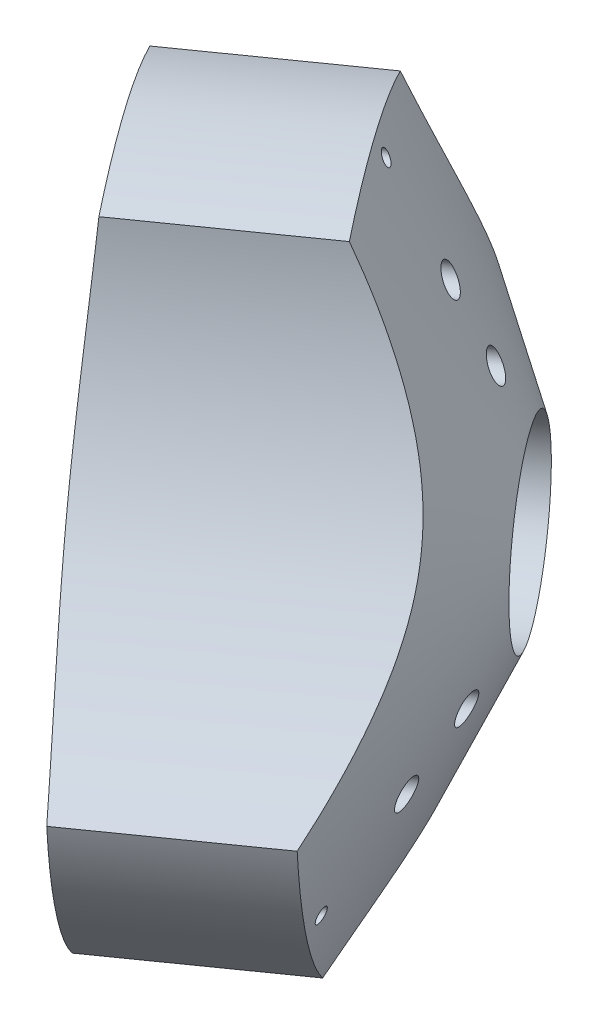
SolidWorks part; units mm, degrees
material "ABS"
ref_plane "前视基准面" through (0, 0, 0) normal (0, 0, 1) x (1, 0, 0)
ref_plane "上视基准面" through (0, 0, 0) normal (0, 1, 0) x (1, 0, 0)
ref_plane "右视基准面" through (0, 0, 0) normal (1, 0, 0) x (0, 0, -1)
other "Configuration Table"
sketch "草图1" plane through (0, 0, 0) normal (0, 1, 0) x (1, 0, 0)
  line L0 (0, 0) -> (50000, 0) construction
  line L1 (0, 0) -> (43301.2702, 25000) construction
  line L2 (0, 0) -> (24999.9997, 43301.2703) construction
  line L3 (0, 0) -> (0, 50000) construction
  line L4 (0, 0) -> (-25000, 43301.2702) construction
  line L5 (0, 0) -> (-43301.2703, 24999.9997) construction
  line L6 (23.1116, -40.0305) -> (43.904, -25.348)
  line L7 (43.904, -25.348) -> (88.4526, -51.0682)
  line L8 (88.4526, -51.0682) -> (46.5626, -80.6488)
  line L9 (46.5626, -80.6488) -> (23.1116, -40.0305)
  line L10 (61.6152, -70.0195) -> (55.8469, -61.8508) construction
  line L11 (55.8469, -61.8508) -> (78.9147, -45.5614)
  line L12 (55.8469, -61.8508) -> (41.5417, -71.9524)
  spline S0 degree 4 poles (4.5441, -13.9852) (5.069, -13.9115) (6.1117, -13.7144) (7.5966, -13.2868) (9.4525, -12.4738) (11.1485, -11.4611) (12.673, -10.2854) (14.0902, -8.9027) (15.2006, -7.528) (16.0517, -6.2294) (16.6357, -5.1571) (16.9969, -4.4036) (17.2795, -3.7437) (17.4701, -3.2541) (17.647, -2.7595) (17.7869, -2.3315) (17.8956, -1.9726) (17.9965, -1.6106) (18.0724, -1.3201) (18.1431, -1.0312) (18.201, -0.7763) (18.2495, -0.5466) (18.2961, -0.3139) (18.338, -0.0934) (18.3688, 0.0809) (18.404, 0.2961) (18.438, 0.517) (18.4698, 0.7375) (18.5019, 0.9839) (18.5336, 1.2626) (18.5616, 1.5443) (18.5855, 1.8273) (18.6051, 2.1103) (18.6204, 2.3933) (18.6344, 2.7473) (18.6427, 3.1726) (18.6402, 3.6687) (18.606, 4.6606) (18.4743, 6.0736) (18.1443, 7.891) (17.4882, 10.0676) (16.5951, 12.1579) (15.4804, 14.1385) (14.1536, 15.9992) (12.6297, 17.7192) (10.7951, 19.3989) (8.6272, 20.9716) (6.1287, 22.3558) (3.3088, 23.4722) (0.3713, 24.2251) (-2.6362, 24.611) (-5.6679, 24.6319) (-8.6804, 24.2953) (-11.6337, 23.6131) (-14.4905, 22.6011) (-17.8988, 20.9477) (-21.6682, 18.3857) (-25.4815, 14.66) (-28.8831, 9.6089) (-31.2279, 3.9916) (-32.5355, -2.3024) (-32.5832, -9.4982) (-30.886, -17.2942) (-27.0418, -25.1548) (-21.1423, -32.1629) (-13.78, -37.6027) (-5.394, -41.2569) (3.5764, -43.0207) (12.7127, -42.8868) (21.6333, -40.9289) (30.0036, -37.2857) (37.5425, -32.1439) (44.0239, -25.7248) (49.277, -18.2707) (53.1837, -10.0336) (55.6748, -1.2666) (56.7255, 7.7843) (56.3496, 16.8863) (54.5948, 25.8236) (51.5367, 34.4007) (47.2736, 42.4454) (41.6252, 50.2165) (33.2939, 58.6988) (21.6024, 66.7973) (6.2316, 72.9489) (-11.9297, 75.3897) (-30.1426, 73.5037) (-47.4501, 67.5662) (-63.0493, 58.0235) (-76.3038, 45.4399) (-86.7456, 30.4509) (-94.067, 13.7235) (-98.1075, -4.0757) (-98.837, -22.3066) (-96.337, -40.374) (-90.7813, -57.7411) (-82.4178, -73.9383) (-71.5503, -88.568) (-58.5225, -101.306) (-43.7037, -111.9004) (-27.476, -120.169) (-10.2235, -125.9948) (7.6766, -129.3207) (25.8616, -130.1437) (43.989, -128.5088) (59.522, -125.003) (72.4202, -120.5917) (82.8104, -116.0253) (90.8771, -111.8583) (98.6697, -107.1992) (106.1617, -102.071) (114.2246, -95.801) (122.6763, -88.2215) (131.2888, -79.1727) (139.0767, -69.4058) (144.8157, -60.9536) (149.48, -53.1674) (153.2371, -46.1706) (156.1751, -40.0285) (158.8259, -33.7588) (160.8418, -28.4575) (162.3378, -24.1741) (163.5443, -20.3917) (164.5049, -17.1274) (165.2564, -14.393) (165.828, -12.1982) (166.3703, -9.9944) (166.8184, -8.0627) (167.1848, -6.398) (167.4765, -5.0161) (167.7053, -3.8925) (167.892, -2.9476) (168.0629, -2.0497) (168.1956, -1.3461) (168.4043, -0.1916) (168.4882, 0.2863) (168.6688, 1.3366) (168.7622, 1.9047) (168.8711, 2.5704) (169.0198, 3.5044) (169.1948, 4.6573) (169.389, 6.0027) (169.5701, 7.3351) (169.7422, 8.6768) (169.9433, 10.3507) (170.1641, 12.3645) (170.391, 14.7154) (170.6086, 17.4069) (170.7844, 20.1009) (170.9186, 22.7976) (171.0111, 25.4959) (171.0621, 28.1953) (171.0718, 30.8952) (171.0401, 33.595) (170.9491, 36.9686) (170.6302, 43.7113) (169.6923, 53.7988) (167.722, 65.8035) (165.138, 76.2991) (163.208, 82.7681) (162.3863, 85.3399) knots 0 0 0 0 0 0.002183 0.004365 0.006343 0.00832 0.010298 0.012275 0.014479 0.01558 0.016682 0.0173 0.017918 0.018536 0.018845 0.019463 0.019772 0.020081 0.02039 0.020699 0.021008 0.021162 0.021317 0.021626 0.021918 0.022064 0.02221 0.022501 0.022793 0.023085 0.023377 0.023669 0.023961 0.024253 0.024544 0.025128 0.025712 0.026296 0.028631 0.030966 0.033302 0.035637 0.037972 0.040307 0.042695 0.045083 0.048197 0.05131 0.054424 0.057538 0.060652 0.063766 0.066879 0.069993 0.073107 0.07622 0.082448 0.088676 0.094903 0.10113 0.107357 0.114993 0.124334 0.133675 0.143016 0.152357 0.161699 0.17104 0.18038 0.189722 0.199063 0.208404 0.217745 0.227086 0.236427 0.245769 0.25511 0.264451 0.273792 0.283133 0.292474 0.301815 0.313225 0.331907 0.35059 0.369272 0.387954 0.406636 0.425318 0.444001 0.462683 0.481365 0.500047 0.518729 0.537412 0.556094 0.574776 0.593458 0.612141 0.630823 0.649505 0.668187 0.68687 0.705552 0.724234 0.742916 0.752258 0.761599 0.77094 0.780281 0.789622 0.798963 0.812975 0.826987 0.840998 0.85034 0.85501 0.864351 0.873692 0.878363 0.883033 0.887704 0.892374 0.89471 0.897045 0.89938 0.901716 0.904051 0.905219 0.906387 0.907554 0.908722 0.909306 0.90989 0.911057 0.912447 0.912794 0.913142 0.913837 0.915226 0.916616 0.918006 0.919396 0.920785 0.922175 0.924955 0.927734 0.930513 0.933293 0.936072 0.938852 0.941631 0.944411 0.94719 0.94997 0.955529 0.972205 0.988882 1 1 1 1 1 construction
  spline S1 degree 4 poles (18.3541, 0) (18.3651, 0.0621) (18.381, 0.1554) (18.404, 0.2961) (18.438, 0.517) (18.4698, 0.7375) (18.5019, 0.9839) (18.5336, 1.2626) (18.5616, 1.5443) (18.5855, 1.8273) (18.6051, 2.1103) (18.6204, 2.3933) (18.6344, 2.7473) (18.6427, 3.1726) (18.6402, 3.6687) (18.606, 4.6606) (18.4743, 6.0736) (18.1443, 7.891) (17.4882, 10.0676) (16.5951, 12.1579) (15.4804, 14.1385) (14.1536, 15.9992) (12.6297, 17.7192) (10.7951, 19.3989) (8.6272, 20.9716) (6.1287, 22.3558) (3.3088, 23.4722) (0.3713, 24.2251) (-2.6362, 24.611) (-5.6679, 24.6319) (-8.6804, 24.2953) (-11.6337, 23.6131) (-14.4905, 22.6011) (-17.8988, 20.9477) (-21.6682, 18.3857) (-25.4815, 14.66) (-28.8831, 9.6089) (-31.2279, 3.9916) (-32.5355, -2.3024) (-32.5832, -9.4982) (-30.886, -17.2942) (-27.0418, -25.1548) (-21.1423, -32.1629) (-13.78, -37.6027) (-5.394, -41.2569) (3.5764, -43.0207) (12.7127, -42.8868) (21.6333, -40.9289) (30.0036, -37.2857) (37.5425, -32.1439) (44.0239, -25.7248) (49.277, -18.2707) (53.1837, -10.0336) (55.6748, -1.2666) (56.7255, 7.7843) (56.3496, 16.8863) (54.5948, 25.8236) (51.5367, 34.4007) (47.2736, 42.4454) (41.6252, 50.2165) (33.2939, 58.6988) (21.6024, 66.7973) (6.2316, 72.9489) (-11.9297, 75.3897) (-30.1426, 73.5037) (-47.4501, 67.5662) (-63.0493, 58.0235) (-76.3038, 45.4399) (-86.7456, 30.4509) (-94.067, 13.7235) (-98.1075, -4.0757) (-98.837, -22.3066) (-96.337, -40.374) (-90.7813, -57.7411) (-82.4178, -73.9383) (-71.5503, -88.568) (-58.5225, -101.306) (-43.7037, -111.9004) (-27.476, -120.169) (-10.2235, -125.9948) (7.6766, -129.3207) (25.8616, -130.1437) (43.989, -128.5088) (59.522, -125.003) (72.4202, -120.5917) (82.8104, -116.0253) (90.8771, -111.8583) (98.6697, -107.1992) (106.1617, -102.071) (114.2246, -95.801) (122.6763, -88.2215) (131.2888, -79.1727) (139.0767, -69.4058) (144.8157, -60.9536) (149.48, -53.1674) (153.2371, -46.1706) (156.1751, -40.0285) (158.8259, -33.7588) (160.8418, -28.4575) (162.3378, -24.1741) (163.5443, -20.3917) (164.5049, -17.1274) (165.2564, -14.393) (165.828, -12.1982) (166.3703, -9.9944) (166.8184, -8.0627) (167.1848, -6.398) (167.4765, -5.0161) (167.7053, -3.8925) (167.892, -2.9476) (168.0629, -2.0497) (168.1956, -1.3461) (168.3264, -0.6223) (168.3933, -0.2484) (168.4372, 0) knots 0.021626 0.021626 0.021626 0.021626 0.021626 0.021918 0.022064 0.02221 0.022501 0.022793 0.023085 0.023377 0.023669 0.023961 0.024253 0.024544 0.025128 0.025712 0.026296 0.028631 0.030966 0.033302 0.035637 0.037972 0.040307 0.042695 0.045083 0.048197 0.05131 0.054424 0.057538 0.060652 0.063766 0.066879 0.069993 0.073107 0.07622 0.082448 0.088676 0.094903 0.10113 0.107357 0.114993 0.124334 0.133675 0.143016 0.152357 0.161699 0.17104 0.18038 0.189722 0.199063 0.208404 0.217745 0.227086 0.236427 0.245769 0.25511 0.264451 0.273792 0.283133 0.292474 0.301815 0.313225 0.331907 0.35059 0.369272 0.387954 0.406636 0.425318 0.444001 0.462683 0.481365 0.500047 0.518729 0.537412 0.556094 0.574776 0.593458 0.612141 0.630823 0.649505 0.668187 0.68687 0.705552 0.724234 0.742916 0.752258 0.761599 0.77094 0.780281 0.789622 0.798963 0.812975 0.826987 0.840998 0.85034 0.85501 0.864351 0.873692 0.878363 0.883033 0.887704 0.892374 0.89471 0.897045 0.89938 0.901716 0.904051 0.905219 0.906387 0.907554 0.908722 0.909306 0.90989 0.911057 0.911057 0.911057 0.911057 0.911057
  spline S2 degree 4 poles (26.7771, -19.4547) (27.2791, -18.9699) (28.2564, -17.9726) (29.6389, -16.3973) (31.5138, -13.8737) (32.9647, -11.4834) (34.0651, -9.2998) (34.8847, -7.3726) (35.3191, -6.2309) (35.6599, -5.241) (35.9229, -4.4091) (36.0959, -3.8235) (36.2362, -3.3192) (36.3702, -2.8132) (36.4765, -2.3905) (36.5777, -1.9654) (36.6735, -1.5395) (36.7371, -1.2444) (36.7899, -0.9895) (36.8338, -0.7701) (36.8689, -0.5895) (36.9122, -0.3614) (36.9643, -0.079) (37.0022, 0.137) (37.056, 0.4587) (37.1011, 0.7414) (37.1347, 0.96) (37.1737, 1.2255) (37.2176, 1.5413) (37.2661, 1.9157) (37.3167, 2.3441) (37.3624, 2.772) (37.4133, 3.3079) (37.4649, 3.9519) (37.524, 4.9191) (37.5642, 6.2107) (37.5499, 8.58) (37.2749, 12.0191) (36.4953, 16.2666) (34.9181, 21.2023) (32.7382, 25.9024) (30.2297, 29.9345) (27.5748, 33.3344) (24.3272, 36.7897) (20.4102, 40.1789) (15.3713, 43.5302) (9.113, 46.471) (2.4987, 48.4837) (-3.4771, 49.4179) (-8.6498, 49.6296) (-15.5372, 49.2939) (-22.3494, 48.0444) (-29.7217, 45.4984) (-37.3047, 41.3681) (-42.9225, 37.3494) (-49.2948, 31.5248) (-55.7813, 23.4083) (-61.4472, 12.6507) (-65.4181, -1.9048) (-66.0143, -20.496) (-61.2011, -38.6277) (-51.6663, -54.6681) (-39.5267, -67.0168) (-28.241, -75.0457) (-15.7631, -81.0448) (-2.4709, -84.9082) (11.2641, -86.5959) (25.0917, -86.1269) (38.6859, -83.5703) (51.7521, -79.0376) (62.4941, -73.4702) (71.067, -67.6625) (77.7289, -62.1925) (82.7475, -57.4634) (87.4361, -52.4071) (91.7776, -47.05) (95.7571, -41.4189) (99.3618, -35.5409) (102.1786, -30.2056) (104.3465, -25.5122) (105.8226, -21.9278) (106.7439, -19.5134) (107.4694, -17.486) (108.0246, -15.8552) (108.5543, -14.216) (109.0585, -12.5687) (109.5372, -10.914) (109.9904, -9.2519) (110.418, -7.5833) (110.7697, -6.1172) (111.0551, -4.8577) (111.2824, -3.8044) (111.4574, -2.9629) (111.6056, -2.2213) (111.7181, -1.6396) (111.796, -1.2276) (111.8764, -0.7956) (111.9824, -0.2107) (112.0406, 0.1173) (112.149, 0.7476) (112.2197, 1.1704) (112.2736, 1.499) (112.3401, 1.912) (112.4454, 2.5814) (112.5828, 3.4978) (112.7468, 4.6683) (112.9181, 6.007) (113.1127, 7.6834) (113.3147, 9.6981) (113.5046, 12.0531) (113.6588, 14.7487) (113.7504, 17.4473) (113.7796, 20.1472) (113.7303, 24.197) (113.4243, 30.2662) (112.8255, 35.6383) (112.0569, 40.3021) (111.5392, 42.9519) knots 0 0 0 0 0 0.005611 0.011222 0.016833 0.02525 0.028055 0.030861 0.033666 0.035069 0.036472 0.037875 0.038576 0.039277 0.04068 0.041381 0.042083 0.042784 0.043135 0.043486 0.043836 0.044187 0.044888 0.045754 0.046187 0.04662 0.047052 0.047485 0.048351 0.049216 0.050082 0.050948 0.051813 0.053545 0.055276 0.058738 0.062201 0.072588 0.082976 0.093363 0.103751 0.114138 0.121063 0.127988 0.141838 0.155688 0.169538 0.183388 0.197238 0.204163 0.211088 0.238788 0.252638 0.266488 0.280339 0.294189 0.321888 0.349589 0.377289 0.414571 0.469971 0.497671 0.525371 0.553071 0.580771 0.608471 0.636171 0.663871 0.691571 0.719271 0.746971 0.760821 0.774671 0.788521 0.802371 0.816222 0.830072 0.843922 0.857772 0.864697 0.871622 0.875084 0.878547 0.882009 0.885472 0.888934 0.892397 0.895859 0.899322 0.902784 0.904515 0.906247 0.907978 0.909709 0.910575 0.911008 0.91144 0.913172 0.914528 0.915207 0.915885 0.916563 0.917242 0.918599 0.921312 0.924025 0.926739 0.929452 0.934879 0.940306 0.945732 0.951159 0.956586 0.962013 0.978293 1 1 1 1 1 construction
  spline S3 degree 4 poles (36.9778, 0) (36.994, 0.0921) (37.0177, 0.2297) (37.056, 0.4587) (37.1011, 0.7414) (37.1347, 0.96) (37.1737, 1.2255) (37.2176, 1.5413) (37.2661, 1.9157) (37.3167, 2.3441) (37.3624, 2.772) (37.4133, 3.3079) (37.4649, 3.9519) (37.524, 4.9191) (37.5642, 6.2107) (37.5499, 8.58) (37.2749, 12.0191) (36.4953, 16.2666) (34.9181, 21.2023) (32.7382, 25.9024) (30.2297, 29.9345) (27.5748, 33.3344) (24.3272, 36.7897) (20.4102, 40.1789) (15.3713, 43.5302) (9.113, 46.471) (2.4987, 48.4837) (-3.4771, 49.4179) (-8.6498, 49.6296) (-15.5372, 49.2939) (-22.3494, 48.0444) (-29.7217, 45.4984) (-37.3047, 41.3681) (-42.9225, 37.3494) (-49.2948, 31.5248) (-55.7813, 23.4083) (-61.4472, 12.6507) (-65.4181, -1.9048) (-66.0143, -20.496) (-61.2011, -38.6277) (-51.6663, -54.6681) (-39.5267, -67.0168) (-28.241, -75.0457) (-15.7631, -81.0448) (-2.4709, -84.9082) (11.2641, -86.5959) (25.0917, -86.1269) (38.6859, -83.5703) (51.7521, -79.0376) (62.4941, -73.4702) (71.067, -67.6625) (77.7289, -62.1925) (82.7475, -57.4634) (87.4361, -52.4071) (91.7776, -47.05) (95.7571, -41.4189) (99.3618, -35.5409) (102.1786, -30.2056) (104.3465, -25.5122) (105.8226, -21.9278) (106.7439, -19.5134) (107.4694, -17.486) (108.0246, -15.8552) (108.5543, -14.216) (109.0585, -12.5687) (109.5372, -10.914) (109.9904, -9.2519) (110.418, -7.5833) (110.7697, -6.1172) (111.0551, -4.8577) (111.2824, -3.8044) (111.4574, -2.9629) (111.6056, -2.2213) (111.7181, -1.6396) (111.796, -1.2276) (111.8764, -0.7956) (111.946, -0.4114) (111.9868, -0.1841) (112.0193, 0) knots 0.044888 0.044888 0.044888 0.044888 0.044888 0.045754 0.046187 0.04662 0.047052 0.047485 0.048351 0.049216 0.050082 0.050948 0.051813 0.053545 0.055276 0.058738 0.062201 0.072588 0.082976 0.093363 0.103751 0.114138 0.121063 0.127988 0.141838 0.155688 0.169538 0.183388 0.197238 0.204163 0.211088 0.238788 0.252638 0.266488 0.280339 0.294189 0.321888 0.349589 0.377289 0.414571 0.469971 0.497671 0.525371 0.553071 0.580771 0.608471 0.636171 0.663871 0.691571 0.719271 0.746971 0.760821 0.774671 0.788521 0.802371 0.816222 0.830072 0.843922 0.857772 0.864697 0.871622 0.875084 0.878547 0.882009 0.885472 0.888934 0.892397 0.895859 0.899322 0.902784 0.904515 0.906247 0.907978 0.909709 0.910575 0.911008 0.91144 0.913172 0.913172 0.913172 0.913172 0.913172
  dimension "D1" = 10
revolve "旋转1" add sketch "草图1" angle 360 about L8 region at (48.456, 0, 47.2673) region at (33.862, 0, 33.2606)
ref_plane "基准面1" through (-6.1839, 0, 4.3668) normal (-0.8169, 0, 0.5768) x (0.5768, 0, 0.8169)
sketch "草图2" plane through (-6.1839, 0, 4.3668) normal (-0.8169, 0, 0.5768) x (0.5768, 0, 0.8169)
  line L0 (92.7379, 46.7069) -> (92.7379, 44.2069)
  line L1 (92.7379, 0) -> (92.7379, 20) construction
  line L2 (92.7379, 20) -> (92.7379, 30) construction
  line L4 (92.7379, 0) -> (11.7645, 46.75) construction
  circle A0 centre (92.7379, 0) radius 46.7069 construction
  circle A1 centre (92.7379, 44.2069) radius 1
  circle A3 centre (92.7379, 30) radius 2
  circle A4 centre (92.7379, 20) radius 2
  circle A5 centre (11.7645, 46.75) radius 66
  circle A6 centre (173.7113, 46.75) radius 66
  circle A7 centre (131.0222, -22.1034) radius 1
  circle A9 centre (118.7186, -15) radius 2
  circle A10 centre (110.0584, -10) radius 2
  circle A11 centre (92.7379, -93.5) radius 66
  circle A12 centre (54.4536, -22.1034) radius 1
  circle A14 centre (66.7571, -15) radius 2
  circle A15 centre (75.4174, -10) radius 2
  circle A16 centre (92.7379, 0) radius 12.5
  point P5 (92.7379, 0)
  dimension "D5" = 2
  dimension "D7" = 4
  dimension "D8" = 4
  dimension "D10" = 132
  dimension "D4" = 25
  dimension "D1" = 2.5
  dimension "D2" = 20
  dimension "D3" = 10
  dimension "D9" = 60
  dimension "D11" = 3
extrude "切除-拉伸1" cut sketch "草图2" against normal blind 70 contours A5 | A6 | A11 | A1 | A3 | A4 | A15 | A14 | A12 | A10 | A9 | A7 | A16 region at (46.9137, 43.5198, 79.5598) region at (47.31, 30, 80.1211) region at (47.31, 20, 80.1211) region at (0.6022, 46.75, 13.9768) region at (94.0179, 46.75, 146.2653) region at (69.3936, -22.1034, 111.3941) region at (62.2965, -15, 101.3438) region at (57.301, -10, 94.2696) region at (47.31, -93.5, 80.1211) region at (25.2265, -22.1034, 48.848) region at (32.3236, -15, 58.8983) region at (37.3191, -10, 65.9726) region at (47.31, 0, 80.1211)
fillet "圆角1" radius 3.5 1 edges at (40.2865, 0, 69.7783)
shell "抽壳1" thickness 2
ref_plane "基准面2" through (52.3403, 0, 74.1205) normal (0.5768, 0, 0.8169) x (0.8169, 0, -0.5768)
ref_plane "基准面3" through (53.494, 0, 75.7543) normal (0.5768, 0, 0.8169) x (0.8169, 0, -0.5768)
sketch "草图4" plane through (53.494, 0, 75.7543) normal (0.5768, 0, 0.8169) x (0.8169, 0, -0.5768)
  line L1 (-4.82, 26.4682) -> (29.7219, 26.4682)
  line L3 (-4.82, 26.4682) -> (-4.82, 23.4101)
  line L4 (-4.82, 23.4101) -> (29.7219, 23.4101)
  line L5 (29.7219, 26.4682) -> (29.7219, 23.4101)
  line L6 (-5.4107, 16.321) -> (34.5242, 16.321)
  line L7 (-5.4107, 16.321) -> (-5.4107, 13.9697)
  line L8 (-5.4107, 13.9697) -> (34.5242, 13.9697)
  line L9 (34.5242, 16.321) -> (34.5242, 13.9697)
extrude "凸台-拉伸1" add sketch "草图4" along normal mid plane 1
ref_axis "基准轴1" through (72.7234, 0, 62.1753) along (-0.8169, 0, 0.5768)
pattern_circular "阵列(圆周)1" count 3 over 360 about axis through (72.7234, 0, 62.1753) along (-0.8169, 0, 0.5768) of "凸台-拉伸1"
